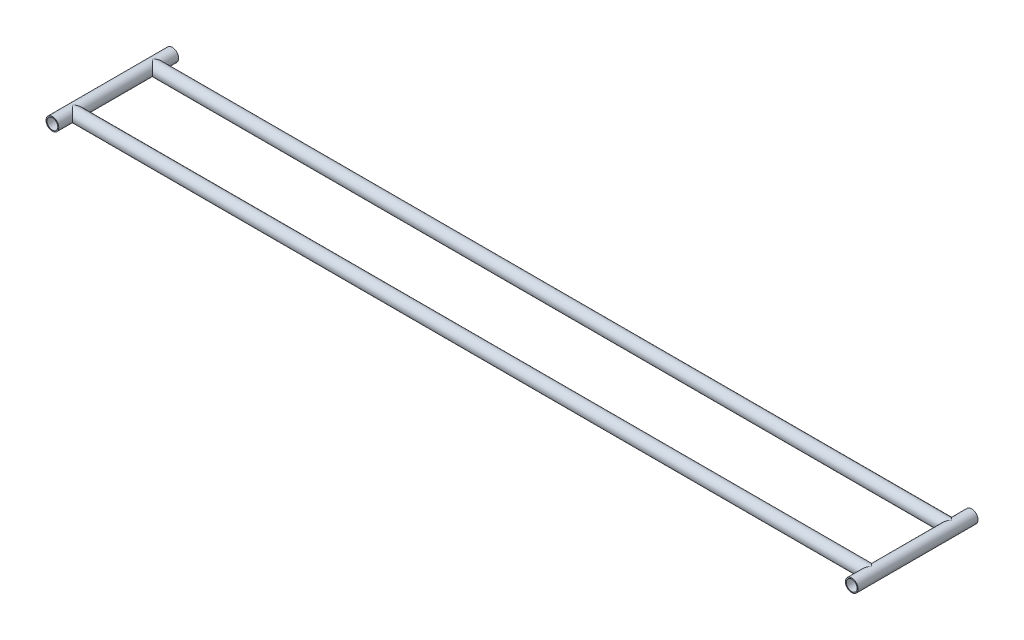
SolidWorks part; units mm, degrees
material "PVC Rigid"
ref_plane "Front Plane" through (0, 0, 0) normal (0, 0, 1) x (1, 0, 0)
ref_plane "Top Plane" through (0, 0, 0) normal (0, 1, 0) x (1, 0, 0)
ref_plane "Right Plane" through (0, 0, 0) normal (1, 0, 0) x (0, 0, -1)
sketch "Sketch1" plane through (0, 0, 0) normal (1, 0, 0) x (0, 0, -1)
  line L0 (-71.0406, 0) -> (82.5769, 0) construction
  circle A0 centre (-50, 0) radius 8
  circle A1 centre (-50, 0) radius 6.75
  circle A2 centre (50, 0) radius 6.75
  circle A3 centre (50, 0) radius 8
  point P6 (-50, 0)
  dimension "D1" = 16
  dimension "D2" = 13.5
  dimension "D3" = 13.5
  dimension "D4" = 16
  dimension "D5" = 50
  dimension "D6" = 50
extrude "Boss-Extrude1" add sketch "Sketch1" along normal blind 1000
sketch "Sketch2" plane through (0, 0, 0) normal (0, 0, 1) x (1, 0, 0)
  circle A0 centre (0, 0) radius 8
  circle A1 centre (0, 0) radius 6.75
  dimension "D1" = 13.5
  dimension "D2" = 16
extrude "Boss-Extrude2" add sketch "Sketch2" along normal blind 75 and the other way blind 75
sketch "Sketch3" plane through (0, 0, 75) normal (0, 0, 1) x (1, 0, 0)
  circle A0 centre (0, 0) radius 6.75
  dimension "D1" = 13.5
extrude "Cut-Extrude1" cut sketch "Sketch3" against normal blind 150
sketch "Sketch4" plane through (0, 0, 0) normal (0, 0, 1) x (1, 0, 0)
  line L0 (1000, -8) -> (1000, 8) construction
  circle A0 centre (1000, 0) radius 8
  circle A1 centre (1000, 0) radius 6.75
  dimension "D1" = 16
  dimension "D2" = 13.5
extrude "Boss-Extrude3" add sketch "Sketch4" along normal blind 75 and the other way blind 75
sketch "Sketch6" plane through (0, 0, 75) normal (0, 0, 1) x (1, 0, 0)
  line L0 (1000, -6.75) -> (1000, 6.75) construction
  circle A0 centre (1000, 0) radius 6.75
  dimension "D1" = 13.5
extrude "Cut-Extrude2" cut sketch "Sketch6" against normal blind 150
